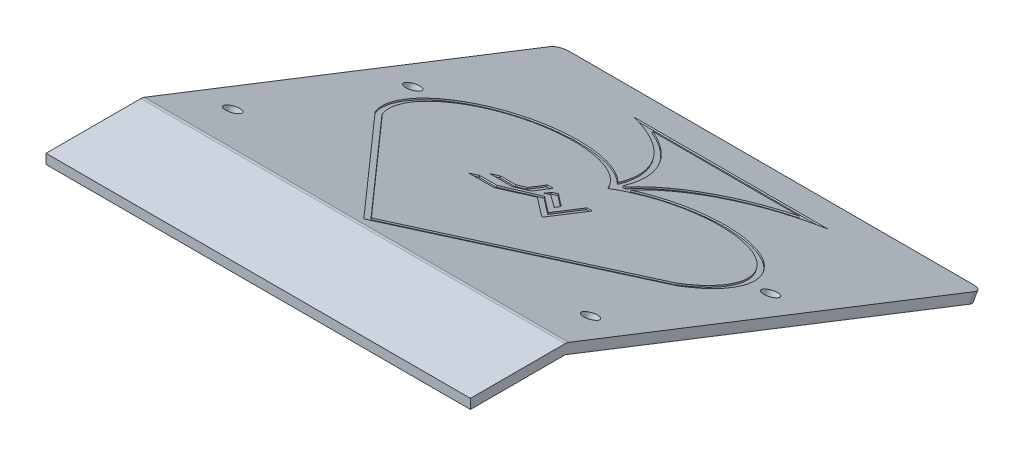
SolidWorks part; units mm, degrees
ref_plane "Plano frontal" through (0, 0, 0) normal (0, 0, 1) x (1, 0, 0)
ref_plane "Plano superior" through (0, 0, 0) normal (0, 1, 0) x (1, 0, 0)
ref_plane "Plano direito" through (0, 0, 0) normal (1, 0, 0) x (0, 0, -1)
sketch "Esboço1" plane through (0, 0, 0) normal (1, 0, 0) x (0, 0, -1)
  line L0 (0, 2) -> (19.99, 2)
  line L1 (19.61, 0) -> (0, 0)
  line L2 (19.99, 2) -> (106.12, -31.7453)
  line L3 (105.11, -33.4985) -> (19.61, 0)
  line L4 (0, 2) -> (0, 0)
  line L5 (106.12, -31.7453) -> (105.11, -33.4985)
  dimension "D1" = 19.61
  dimension "D2" = 19.99
  dimension "D3" = 105.11
  dimension "D4" = 106.12
  dimension "D5" = 2
  dimension "D6" = 31.7453
extrude "Ressalto-extrusão1" add sketch "Esboço1" along normal blind 87.78
sketch "Esboço2" plane through (0, 8.5236, -3.3395) normal (0, 0.9311, -0.3648) x (1, 0, 0)
  circle A0 centre (80.8, 30.5876) radius 1.55 construction
  circle A1 centre (80.8, 30.5876) radius 1.55
  circle A2 centre (6.8, 30.5876) radius 1.55 construction
  circle A3 centre (6.8, 30.5876) radius 1.55
  circle A4 centre (80.8, 70.5876) radius 1.55 construction
  circle A5 centre (80.8, 70.5876) radius 1.55
  circle A6 centre (6.8, 70.5876) radius 1.55 construction
  circle A7 centre (6.8, 70.5876) radius 1.55
extrude "Corte-extrusão1" cut sketch "Esboço2" against normal up to surface (2.0008 mm away) up to face at (43.89, -16.7493, -62.36)
fillet "Filete1" radius 2 2 edges at (0, -32.6219, -105.615) (87.78, -32.6219, -105.615)
fillet "Filete2" radius 2 1 edges at (43.89, 2, -19.99)
sketch "Esboço4" plane through (0, 8.5236, -3.3395) normal (0, 0.9311, -0.3648) x (1, 0, 0)
  line L0 (43.89, 21.5519) -> (43.89, 91.5519) construction
  line L1 (99.9585, 56.5537) -> (-12.1785, 56.55) construction
  line L2 (43.89, 21.5519) -> (13.5797, 56.5509)
  line L3 (43.89, 21.5519) -> (74.2015, 56.5529)
  line L4 (59.0454, 100.3019) -> (28.7346, 100.3019)
  line L5 (87.78, -0.7296) -> (0, -0.7296) construction
  line L6 (87.78, -0.7296) -> (0, -0.7296) construction
  line L7 (43.89, -0.7296) -> (43.89, 4.4324) construction
  line L8 (0, 108.3651) -> (0, 18.2607) construction
  line L9 (0, 108.3651) -> (0, 18.2607) construction
  circle A0 centre (43.89, 56.5519) radius 17.5 construction
  circle A1 centre (43.89, 39.0519) radius 17.5 construction
  circle A2 centre (28.7346, 47.8019) radius 17.5 construction
  circle A3 centre (59.0454, 47.8019) radius 17.5 construction
  arc A4 (43.89, 74.0519) -> (13.5797, 56.5509) centre (28.7346, 65.3019) ccw
  arc A5 (74.2015, 56.5529) -> (43.89, 74.0519) centre (59.0454, 65.3019) ccw
  circle A6 centre (28.7346, 30.3019) radius 17.5 construction
  circle A7 centre (59.0454, 30.3019) radius 17.5 construction
  circle A8 centre (43.89, 74.0519) radius 17.5 construction
  circle A9 centre (28.7346, 82.8019) radius 17.5 construction
  circle A10 centre (59.0454, 82.8019) radius 17.5 construction
  arc A11 (59.0454, 100.3019) -> (43.89, 74.0519) centre (74.2009, 74.0519) ccw
  arc A12 (43.89, 74.0519) -> (28.7346, 100.3019) centre (13.5791, 74.0519) ccw
  arc A13 (43.89, 74.0519) -> (43.89, 56.5519) centre (28.7346, 65.3019) cw construction
  arc A14 (28.7346, 47.8019) -> (43.89, 56.5519) centre (28.7346, 65.3019) ccw construction
  arc A15 (43.89, 56.5519) -> (28.7346, 47.8019) centre (28.7346, 65.3019) cw construction
  arc A16 (28.7346, 47.8019) -> (24.7873, 48.2528) centre (28.7346, 65.3019) cw construction
  arc A17 (17.9085, 51.5525) -> (24.7873, 48.2528) centre (28.7346, 65.3019) ccw construction
  arc A18 (24.7873, 48.2528) -> (17.9085, 51.5525) centre (28.7346, 65.3019) cw construction
  arc A19 (17.9085, 51.5525) -> (13.5797, 56.5509) centre (28.7346, 65.3019) cw construction
  arc A20 (13.5797, 56.5509) -> (17.9085, 51.5525) centre (28.7346, 65.3019) ccw construction
  arc A21 (43.89, 56.5519) -> (43.89, 74.0519) centre (28.7346, 65.3019) ccw construction
  arc A22 (43.89, 74.0519) -> (43.89, 56.5519) centre (59.0454, 65.3019) ccw construction
  arc A23 (43.89, 56.5519) -> (59.0454, 47.8019) centre (59.0454, 65.3019) ccw construction
  arc A24 (59.0454, 47.8019) -> (69.87, 51.5512) centre (59.0454, 65.3019) ccw construction
  arc A25 (69.87, 51.5512) -> (74.2015, 56.5529) centre (59.0454, 65.3019) ccw construction
  point P4 (43.89, 56.5519)
  point P28 (13.5797, 56.5509)
  point P34 (43.89, 56.5519)
  point P35 (74.2015, 56.5529)
  dimension "D2" = 35
  dimension "D1" = 70
  dimension "D3" = 57.28
sketch "Esboço5" plane through (0, 8.5236, -3.3395) normal (0, 0.9311, -0.3648) x (1, 0, 0)
  line L0 (59.0454, 100.3019) -> (28.7346, 100.3019) construction
  line L1 (43.89, 21.5519) -> (74.2015, 56.5529) construction
  line L2 (43.89, 21.5519) -> (13.5797, 56.5509) construction
  line L3 (59.0454, 100.3019) -> (28.7346, 100.3019)
  line L4 (43.89, 21.5519) -> (74.2015, 56.5529)
  line L5 (43.89, 21.5519) -> (13.5797, 56.5509)
  line L6 (43.89, 19.8716) -> (12.6806, 55.9088)
  line L7 (43.89, 19.8716) -> (75.1006, 55.9109)
  line L8 (63.9416, 101.4019) -> (23.8384, 101.4019)
  line L9 (59.0454, 101.4019) -> (28.7346, 101.4019) construction
  line L10 (43.6636, 77.75) -> (44.1164, 77.75)
  arc A0 (43.89, 74.0519) -> (28.7346, 100.3019) centre (13.5791, 74.0519) ccw construction
  arc A1 (59.0454, 100.3019) -> (43.89, 74.0519) centre (74.2009, 74.0519) ccw construction
  arc A2 (74.2015, 56.5529) -> (43.89, 74.0519) centre (59.0454, 65.3019) ccw construction
  arc A3 (43.89, 74.0519) -> (13.5797, 56.5509) centre (28.7346, 65.3019) ccw construction
  arc A4 (43.6636, 77.75) -> (28.7346, 100.3019) centre (13.5791, 74.0519) ccw
  arc A5 (59.0454, 100.3019) -> (44.1164, 77.75) centre (74.2009, 74.0519) ccw
  arc A6 (74.2015, 56.5529) -> (43.89, 74.0519) centre (59.0454, 65.3019) ccw
  arc A7 (43.89, 74.0519) -> (13.5797, 56.5509) centre (28.7346, 65.3019) ccw
  arc A9 (75.1006, 55.9109) -> (45.225, 77.75) centre (59.0454, 65.3019) ccw
  arc A10 (42.555, 77.75) -> (23.8384, 101.4019) centre (13.5791, 74.0519) ccw
  arc A11 (63.9416, 101.4019) -> (45.225, 77.75) centre (74.2009, 74.0519) ccw
  arc A12 (59.5954, 99.3492) -> (44.99, 74.0519) centre (74.2009, 74.0519) ccw construction
  arc A13 (42.79, 74.0519) -> (28.1846, 99.3492) centre (13.5791, 74.0519) ccw construction
  arc A14 (43.89, 74.0519) -> (28.7346, 100.3019) centre (13.5791, 74.0519) ccw construction
  arc A15 (59.0454, 100.3019) -> (43.89, 74.0519) centre (74.2009, 74.0519) ccw construction
  arc A17 (75.1006, 55.9109) -> (43.89, 76.0848) centre (59.0454, 65.3019) ccw construction
  arc A18 (42.555, 77.75) -> (12.6806, 55.9088) centre (28.7346, 65.3019) ccw
  arc A19 (43.89, 76.0848) -> (12.6806, 55.9088) centre (28.7346, 65.3019) ccw construction
  dimension "D2" = 60.6218
  dimension "D3" = 1.1
  dimension "D4" = 1.1
  dimension "D1" = 1.1
  dimension "D5" = 1.1
extrude "Corte-extrusão2" cut sketch "Esboço5" against normal blind 0.3 contours A10 A18 L6 L7 A9 A11 L8 L3 A5 L10 A4 A7 A6 L4 L5 region at (29.0855, -5.5514, -39.2638)
sketch "Logo_MF" plane through (0, 8.5236, -3.3395) normal (0, 0.9311, -0.3648) x (1, 0, 0)
  line L0 (49.9626, 64.155) -> (48.829, 64.155)
  line L1 (48.829, 64.155) -> (48.829, 55.5351)
  line L2 (48.829, 55.5351) -> (43.89, 60.0216)
  line L3 (43.89, 60.0216) -> (38.9069, 54.7788)
  line L4 (38.9069, 54.7788) -> (35.3881, 54.7788)
  line L5 (35.3881, 54.7788) -> (34.2601, 53.537)
  line L6 (34.2601, 53.537) -> (39.4506, 53.537)
  line L7 (39.4506, 53.537) -> (43.8882, 58.4222)
  line L8 (43.8882, 58.4222) -> (49.9626, 52.9043)
  line L9 (49.9626, 52.9043) -> (49.9626, 64.155)
  line L10 (47.5203, 58.2743) -> (47.5203, 59.8448)
  line L11 (47.5203, 59.8448) -> (43.6399, 63.3698)
  line L12 (43.6399, 63.3698) -> (42.959, 62.6202)
  line L13 (42.959, 62.6202) -> (42.959, 60.9001)
  line L14 (42.959, 60.9001) -> (43.641, 61.6509)
  line L15 (43.641, 61.6509) -> (47.5203, 58.2743)
  line L16 (41.859, 64.155) -> (41.859, 59.313)
  line L17 (41.859, 59.313) -> (39.859, 57.2088)
  line L18 (39.859, 57.2088) -> (35.1755, 57.2088)
  line L19 (35.1755, 57.2088) -> (36.3279, 58.4212)
  line L20 (36.3279, 58.4212) -> (39.4501, 58.4212)
  line L21 (39.4501, 58.4212) -> (40.644, 59.6773)
  line L22 (40.644, 59.6773) -> (40.644, 64.155)
  line L23 (40.644, 64.155) -> (41.859, 64.155)
  line L24 (43.89, 74.0519) -> (43.89, 21.5519) construction
  line L25 (0, 108.3651) -> (0, 18.2607) construction
  line L26 (0, 18.2607) -> (87.78, 18.2607) construction
  dimension "D1" = 2.43
  dimension "D2" = 6.97
  dimension "D3" = 1.1
  dimension "D4" = 34.2601
  dimension "D5" = 35.1755
  dimension "D6" = 35.3881
  dimension "D7" = 36.3279
  dimension "D8" = 38.9069
  dimension "D9" = 39.4501
  dimension "D10" = 39.4506
  dimension "D11" = 39.859
  dimension "D12" = 40.644
  dimension "D13" = 41.859
  dimension "D14" = 47.5203
  dimension "D15" = 43.6399
  dimension "D16" = 43.641
  dimension "D17" = 43.8882
  dimension "D18" = 43.89
  dimension "D19" = 49.9626
  dimension "D20" = 34.6436
  dimension "D21" = 87.78
  dimension "D22" = 35.2763
  dimension "D23" = 37.2745
  dimension "D24" = 41.5842
  dimension "D25" = 40.0137
  dimension "D26" = 42.6394
  dimension "D27" = 45.8944
  dimension "D37" = 90.1044
extrude "Corte-extrusão3" cut sketch "Logo_MF" against normal blind 0.3
